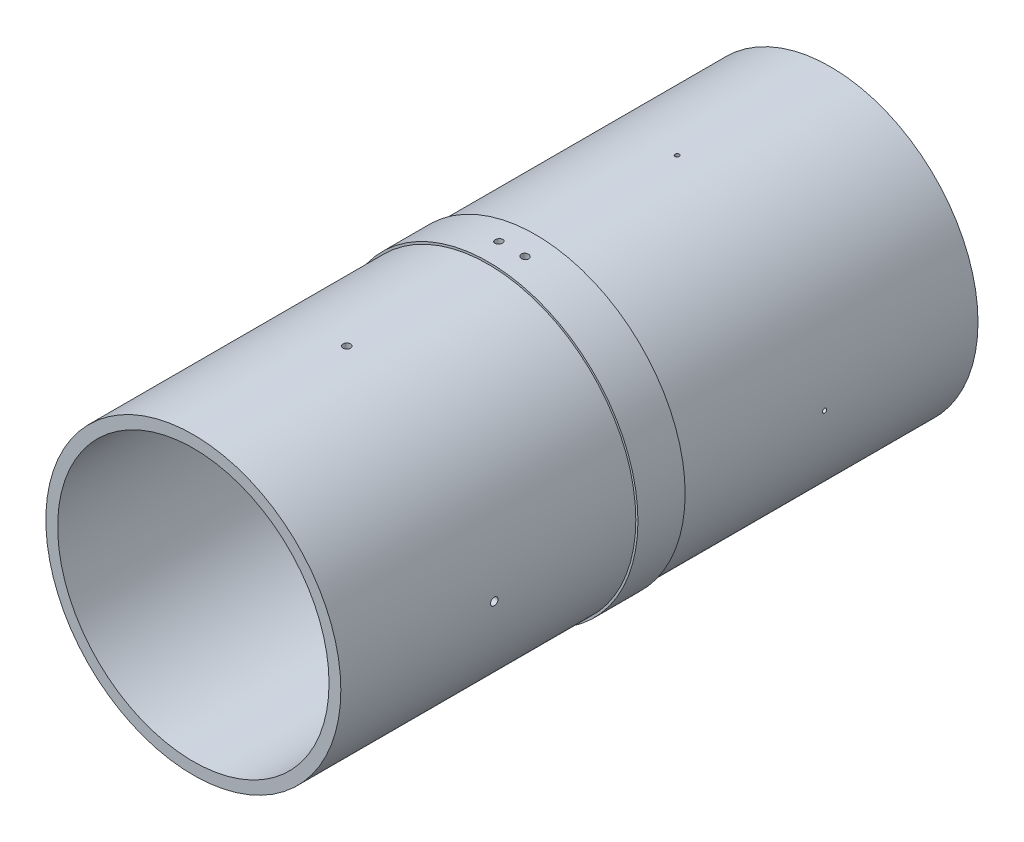
SolidWorks part; units mm, degrees
ref_plane "Front Plane" through (0, 0, 0) normal (0, 0, 1) x (1, 0, 0)
ref_plane "Top Plane" through (0, 0, 0) normal (0, 1, 0) x (1, 0, 0)
ref_plane "Right Plane" through (0, 0, 0) normal (1, 0, 0) x (0, 0, -1)
sketch "Sketch1" plane through (0, 0, 0) normal (0, 0, 1) x (1, 0, 0)
  circle A0 centre (0, 0) radius 79.375
  circle A1 centre (0, 0) radius 73.025
  dimension "D1" = 158.75
  dimension "D2" = 6.35
extrude "Boss-Extrude1" add sketch "Sketch1" along normal blind 342.9
ref_plane "Plane1" through (0, 0, 171.45) normal (0, 0, 1) x (1, 0, 0)
sketch "Sketch2" plane through (0, 0, 171.45) normal (0, 0, 1) x (1, 0, 0)
  circle A0 centre (0, 0) radius 79.375 construction
  circle A1 centre (0, 0) radius 79.375
  circle A2 centre (0, 0) radius 80.518
extrude "Boss-Extrude2" add sketch "Sketch2" against normal mid plane 25.4
sketch "Sketch5" plane through (0, 0, 171.45) normal (0, 0, 1) x (1, 0, 0)
  line L0 (0, 0) -> (0, 47.1719) construction
  line L1 (0, 0) -> (7.0176, 80.2116) construction
  circle A1 centre (0, 0) radius 80.518 construction
  point P2 (0, 0)
  point P5 (8.3839, 95.8285)
  point P7 (0, 0)
  point P8 (0, 0)
  dimension "D1" = 5
ref_plane "Plane2" through (7.0176, 80.2116, 0) normal (0.0872, 0.9962, 0) x (0, 0, 1)
hole_wizard "5/32 (0.15625) Diameter Hole1" positions "Sketch9" profile "Sketch10" hole size "5/32" standard "ANSI Inch" end condition up to next
sketch "Sketch9" plane through (7.0176, 80.2116, 0) normal (0.0872, 0.9962, 0) x (0, 0, 1)
  point P0 (171.45, 0)
sketch "Sketch10" plane through (7.0176, 80.2116, 171.45) normal (0, 0, 1) x (-0.9962, 0.0872, 0)
  line L0 (0, 0) -> (0, 7.493)
  line L1 (0, 7.493) -> (1.9844, 7.493)
  line L2 (1.9844, 7.493) -> (1.9844, 0)
  line L5 (1.9844, 0) -> (0, 0)
  line L11 (0, -6.35) -> (0, 107.95) construction
  dimension "Thru Hole Dia." = 3.9688
  dimension "Thru Hole Depth" = 7.493
mirror "Mirror1" about plane through (0, 0, 0) normal (1, 0, 0) of "5/32 (0.15625) Diameter Hole1"
ref_plane "Plane3" through (0, 79.375, 0) normal (0, 1, 0) x (1, 0, 0)
sketch "Sketch11" plane through (0, 79.375, 0) normal (0, 1, 0) x (1, 0, 0)
  line L0 (80.518, -158.75) -> (-80.518, -158.75) construction
  point P0 (0, -82.55)
  dimension "D1" = 76.2
hole_wizard "#4-40 Tapped Hole1" positions "Sketch12" profile "Sketch13" tap size "#4-40" standard "ANSI Inch" end condition up to next
sketch "Sketch12" plane through (0, 79.375, 0) normal (0, 1, 0) x (1, 0, 0)
  point P0 (0, -82.55)
sketch "Sketch13" plane through (0, 79.375, 82.55) normal (1, 0, 0) x (0, 0, 1)
  line L0 (0, 0) -> (0, 6.35)
  line L1 (0, 6.35) -> (1.1303, 6.35)
  line L2 (1.1303, 6.35) -> (1.1303, 0)
  line L5 (1.1303, 0) -> (0, 0)
  line L11 (0, -6.35) -> (0, 107.95) construction
  dimension "Thru Tap Drill Dia." = 2.2606
  dimension "Thru Tap Drill Depth" = 6.35
cosmetic thread "Hole Thread1" parameters "D2"=2.8448
pattern_circular "CirPattern1" count 4 over 360 about axis through (0, 0, 0) along (0, 0, 1) of "#4-40 Tapped Hole1"
cosmetic thread "Hole Thread2" parameters "D2"=2.8448
cosmetic thread "Hole Thread3" parameters "D2"=2.8448
cosmetic thread "Hole Thread4" parameters "D2"=2.8448
sketch "Sketch14" plane through (0, 79.375, 0) normal (0, 1, 0) x (1, 0, 0)
  line L0 (-79.375, -184.15) -> (79.375, -184.15) construction
  point P0 (0, -260.35)
  dimension "D1" = 76.2
hole_wizard "#10-32 Tapped Hole1" positions "Sketch15" profile "Sketch16" tap size "#10-32" standard "ANSI Inch" end condition up to next
sketch "Sketch15" plane through (0, 79.375, 0) normal (0, 1, 0) x (1, 0, 0)
  point P0 (0, -260.35)
sketch "Sketch16" plane through (0, 79.375, 260.35) normal (1, 0, 0) x (0, 0, 1)
  line L0 (0, 0) -> (0, 6.35)
  line L1 (0, 6.35) -> (2.0193, 6.35)
  line L2 (2.0193, 6.35) -> (2.0193, 0)
  line L5 (2.0193, 0) -> (0, 0)
  line L11 (0, -6.35) -> (0, 107.95) construction
  dimension "Thru Tap Drill Dia." = 4.0386
  dimension "Thru Tap Drill Depth" = 6.35
cosmetic thread "Hole Thread5" parameters "D2"=4.826
pattern_circular "CirPattern2" count 4 over 360 about axis through (0, 0, 342.9) along (0, 0, 1) of "#10-32 Tapped Hole1"
cosmetic thread "Hole Thread6" parameters "D2"=4.826
cosmetic thread "Hole Thread7" parameters "D2"=4.826
cosmetic thread "Hole Thread8" parameters "D2"=4.826
